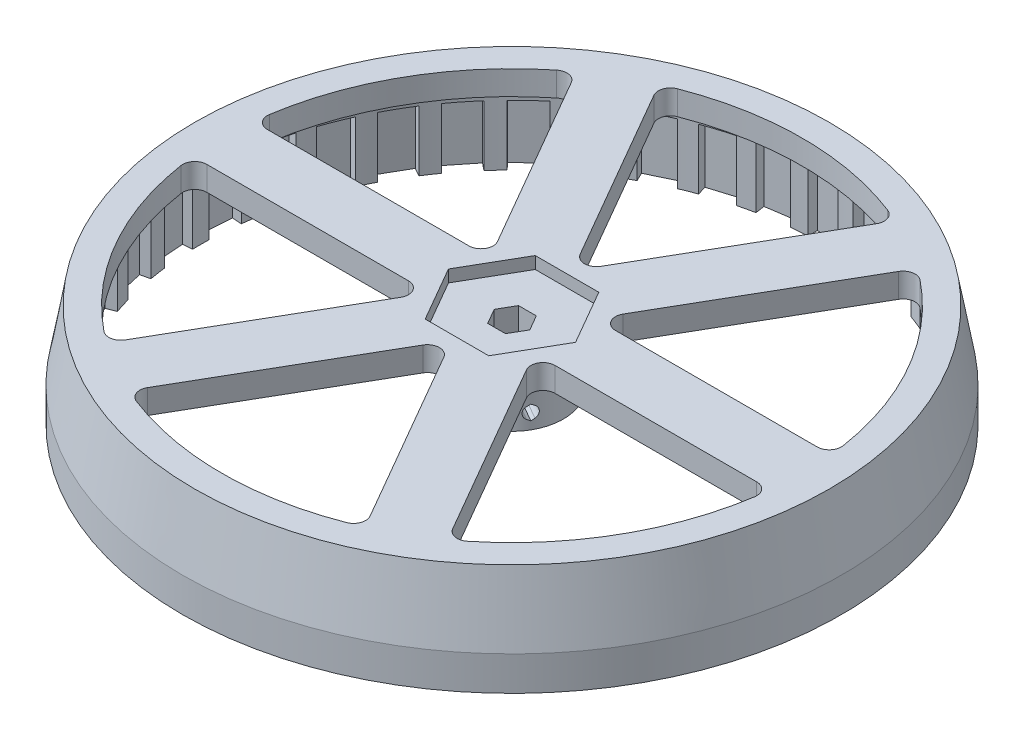
SolidWorks part; units mm, degrees
material "ABS"
ref_plane "Front Plane" through (0, 0, 0) normal (0, 0, 1) x (1, 0, 0)
ref_plane "Top Plane" through (0, 0, 0) normal (0, 1, 0) x (1, 0, 0)
ref_plane "Right Plane" through (0, 0, 0) normal (1, 0, 0) x (0, 0, -1)
sketch "Sketch1" plane through (0, 0, 0) normal (0, 0, 1) x (1, 0, 0)
  line L0 (0, 29) -> (0, 33)
  line L4 (51.5, 29) -> (51.5, 16)
  line L5 (51.5, 16) -> (54.5, 16)
  line L6 (54.5, 16) -> (54.5, 33)
  line L7 (54.5, 33) -> (0, 33)
  line L8 (0, 0) -> (0, 63.0003) construction
  line L11 (0, 29) -> (51.5, 29)
  dimension "D3" = 103
  dimension "D4" = 3
  dimension "D7" = 13
  dimension "D8" = 4
revolve "Main Revolve" add sketch "Sketch1" angle 360 about L8
sketch "Sketch2" plane through (0, 33, 0) normal (0, 1, 0) x (1, 0, 0)
  line L0 (0, 0) -> (0, 75.8468) construction
  line L1 (0, 0) -> (27.25, 47.1984) construction
  line L2 (18.402, 41.8732) -> (1.7321, 13)
  line L3 (-18.402, 41.8732) -> (-1.7321, 13)
  line L4 (0, 0) -> (-27.25, 47.1984) construction
  arc A0 (-17.3947, 44.7373) -> (17.3947, 44.7373) centre (0, 0) cw
  circle A2 centre (0, 0) radius 54.5 construction
  arc A3 (17.3947, 44.7373) -> (18.402, 41.8732) centre (16.67, 42.8732) cw
  arc A6 (-17.3947, 44.7373) -> (-18.402, 41.8732) centre (-16.67, 42.8732) ccw
  arc A8 (1.7321, 13) -> (-1.7321, 13) centre (0, 14) cw
  point P15 (0, 10)
  point P23 (0, 10)
  dimension "D5" = 48
  dimension "D6" = 2
  dimension "D7" = 2
  dimension "D3" = 2
  dimension "D1" = 30
  dimension "D2" = 30
  dimension "D4" = 10
extrude "Slot Cut" cut sketch "Sketch2" against normal through all
pattern_circular "Slot Cut Pattern" count 6 over 360 about axis through (0, 33, 0) along (0, -1, 0) of "Slot Cut"
sketch "Sketch4" plane through (0, 16, 0) normal (0, -1, 0) x (1, 0, 0)
  line L0 (-2.5, 53) -> (2.5, 53)
  line L1 (-2.5, 53) -> (-2.5, 51.4393)
  line L2 (2.5, 53) -> (2.5, 51.4393)
  circle A0 centre (0, 0) radius 51.5 construction
  arc A1 (2.5, 51.4393) -> (-2.5, 51.4393) centre (0, 0) ccw
  point P3 (0, 53)
  dimension "D2" = 1.5
  dimension "D1" = 5
extrude "Magnet Slots" cut sketch "Sketch4" against normal blind 10
pattern_circular "Magnet Cut Pattern" count 42 over 360 about axis through (0, 16, 0) along (0, -1, 0) of "Magnet Slots"
chamfer "Chamfer1" distance 2 angle 80 1 edges at (0, 33, -54.5) first distance on face at (0, 33, 33.6578)
sketch "Sketch5" plane through (0, 33, 0) normal (0, 1, 0) x (1, 0, 0)
  line L1 (2.9445, 0) -> (1.4722, 2.55)
  line L2 (1.4722, 2.55) -> (-1.4722, 2.55)
  line L3 (-1.4722, 2.55) -> (-2.9445, 0)
  line L4 (-2.9445, 0) -> (-1.4722, -2.55)
  line L5 (-1.4722, -2.55) -> (1.4722, -2.55)
  line L6 (1.4722, -2.55) -> (2.9445, 0)
  circle A0 centre (0, 0) radius 2.55 construction
  dimension "D1" = 5.1
extrude "Cut-Extrude1" cut sketch "Sketch5" against normal through all both and the other way through all
sketch "Sketch8" plane through (0, 29, 0) normal (0, -1, 0) x (1, 0, 0)
  line L0 (-1.4722, 2.55) -> (1.4722, 2.55) construction
  line L1 (2.9445, 0) -> (1.4722, 2.55)
  line L2 (1.4722, 2.55) -> (-1.4722, 2.55)
  line L3 (-1.4722, 2.55) -> (-2.9445, 0)
  line L4 (-2.9445, 0) -> (-1.4722, -2.55)
  line L5 (-1.4722, -2.55) -> (1.4722, -2.55)
  line L6 (1.4722, -2.55) -> (2.9445, 0)
  circle A0 centre (0, 0) radius 2.55 construction
  circle A1 centre (0, 0) radius 8.5
  dimension "D1" = 17
extrude "Boss-Extrude1" add sketch "Sketch8" along normal blind 8
sketch "Sketch9" plane through (0, 29, 0) normal (0, -1, 0) x (1, 0, 0)
  circle A0 centre (0, 0) radius 8.5
  circle A1 centre (0, 0) radius 9
  circle A2 centre (0, 0) radius 8.5 construction
  dimension "D1" = 0.5
extrude "Boss-Extrude2" add sketch "Sketch9" along normal blind 1
sketch "Sketch10" plane through (-2.2084, 0, -1.275) normal (0.866, 0, 0.5) x (0.5, 0, -0.866)
  line L0 (0, 26) -> (0, 21) construction
  line L2 (-1.4722, 21) -> (1.4722, 21) construction
  line L4 (2, 26) -> (-2, 26)
  line L5 (2, 26) -> (2, 21)
  line L6 (2, 21) -> (-2, 21)
  line L7 (-2, 26) -> (-2, 21)
  line L8 (2, 26) -> (-2, 21) construction
  line L9 (2, 21) -> (-2, 26) construction
  point P6 (0, 23.5)
  dimension "D1" = 4
  dimension "D2" = 5
extrude "Cut-Extrude2" cut sketch "Sketch10" against normal blind 1.5 and the other way blind 1
extrude "Cut-Extrude3" cut sketch "Sketch10<2>" along normal blind 1.5 and the other way blind 1.5 from surface starting at face at (2.2084, 27, 1.275)
sketch "Sketch10<2>" plane through (-2.2084, 0, -1.275) normal (0.866, 0, 0.5) x (0.5, 0, -0.866) same geometry as "Sketch10"
fillet "Fillet1" radius 0.5 4 edges at (-0.4167, 23.5, -2.55) (2.4167, 23.5, -0.9141) (0.4167, 23.5, 2.55) (-2.4167, 23.5, 0.9141)
sketch "Sketch11" plane through (-3.5074, 0, -2.025) normal (0.866, 0, 0.5) x (0.5, 0, -0.866)
  line L0 (0, 26) -> (0, 21) construction
  line L1 (2, 26) -> (-2, 26) construction
  line L2 (-2, 21) -> (2, 21) construction
  line L3 (0, 23.5) -> (0, 22.3) construction
  line L4 (0, 22.3) -> (-0.5083, 22.5813)
  line L5 (0, 22.3) -> (0.5083, 22.5812)
  line L6 (0, 23.5) -> (0.5997, 23.5) construction
  line L7 (0, 24.7) -> (-0.5083, 24.4187)
  line L8 (0, 24.7) -> (0.5083, 24.4188)
  arc A0 (-0.5083, 24.4187) -> (-0.5083, 22.5813) centre (0, 23.5) ccw
  arc A1 (0.5083, 22.5812) -> (0.5083, 24.4188) centre (0, 23.5) ccw
  dimension "D1" = 2.1
  dimension "D2" = 1.2
extrude "Cut-Extrude4" cut sketch "Sketch11" against normal up to next and the other way blind 15.5 contours L7 A0 L4 L5 A1 L8
sketch "Sketch14" plane through (0, 33, 0) normal (0, 1, 0) x (1, 0, 0)
  line L0 (2.9445, 0) -> (1.4722, 2.55) construction
  line L1 (5.2539, -9.1) -> (10.5078, 0)
  line L2 (10.5078, 0) -> (5.2539, 9.1)
  line L3 (5.2539, 9.1) -> (-5.2539, 9.1)
  line L4 (-5.2539, 9.1) -> (-10.5078, 0)
  line L5 (-10.5078, 0) -> (-5.2539, -9.1)
  line L6 (-5.2539, -9.1) -> (5.2539, -9.1)
  circle A3 centre (0, 0) radius 9.1 construction
  dimension "D1" = 18.2
extrude "Cut-Extrude6" cut sketch "Sketch14" against normal blind 2
equation "\"D3@Sketch1\"=100+2*(1+0.5)"
